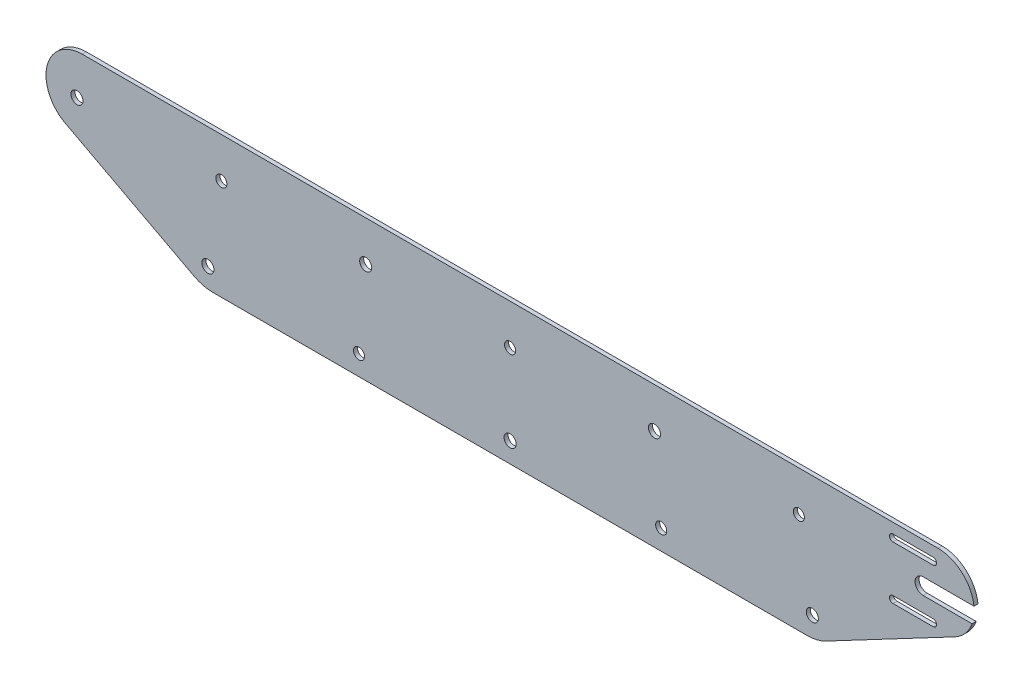
SolidWorks part; units mm, degrees
ref_plane "Plan de face" through (0, 0, 0) normal (0, 0, 1) x (1, 0, 0)
ref_plane "Plan de dessus" through (0, 0, 0) normal (0, 1, 0) x (1, 0, 0)
ref_plane "Plan de droite" through (0, 0, 0) normal (1, 0, 0) x (0, 0, -1)
sketch "Esquisse1" plane through (0, 0, 0) normal (0, 0, 1) x (1, 0, 0)
  line L0 (0, 0) -> (0, 122.747) construction
  line L1 (-215, -20) -> (215, -20) construction
  line L2 (-215, -20) -> (-215, 20) construction
  line L3 (-215, 20) -> (215, 20) construction
  line L4 (215, -20) -> (215, 20) construction
  line L5 (-215, -20) -> (215, 20) construction
  line L6 (-215, 20) -> (215, -20) construction
  line L7 (-1220, 0) -> (-150, 0) construction
  line L8 (-284.959, 40) -> (-150, 40)
  line L9 (150, 40) -> (284.959, 40)
  line L10 (150, 0) -> (150, -20) construction
  line L11 (150, -20) -> (-150, -20) construction
  line L12 (-150, 0) -> (-150, -20) construction
  line L13 (150, 0) -> (-150, -20) construction
  line L14 (150, -20) -> (-150, 0) construction
  line L15 (-284.959, 40) -> (-152.4795, -30)
  line L16 (-152.4795, -30) -> (152.4795, -30)
  line L17 (284.959, 40) -> (152.4795, -30)
  line L18 (-215, 20) -> (-71.6667, 20) construction
  line L19 (-71.6667, 20) -> (71.6667, 20) construction
  line L20 (71.6667, 20) -> (215, 20) construction
  line L21 (150, 0) -> (193.5165, 0) construction
  line L22 (150, 95) -> (-150, 95) construction
  line L23 (150, 95) -> (150, 40) construction
  line L24 (-150, 40) -> (150, 40)
  line L25 (-150, 95) -> (-150, 40) construction
  line L26 (150, 95) -> (-150, 0) construction
  line L27 (150, 0) -> (-150, 95) construction
  circle A0 centre (-215, 20) radius 3
  circle A1 centre (-150, -20) radius 3
  circle A2 centre (150, -20) radius 3
  circle A3 centre (215, 20) radius 3
  circle A4 centre (0, -20) radius 3
  circle A5 centre (-71.6667, 20) radius 3
  circle A6 centre (71.6667, 20) radius 3
  circle A7 centre (0, 78.03) radius 3 construction
  point P0 (0, 0)
  point P8 (0, -10)
  point P20 (0, 47.5)
  point P21 (0, -30)
  point P31 (0, 47.5)
  dimension "D8" = 6
  dimension "D10" = 58.03
  dimension "D1" = 430
  dimension "D2" = 40
  dimension "D3" = 300
  dimension "D4" = 20
  dimension "D5" = 15
  dimension "D6" = 10
  dimension "D7" = 10
  dimension "D9" = 55
extrude "Boss.-Extru.1" add sketch "Esquisse1" along normal blind 2
fillet "Congé1" radius 18 2 edges at (-284.959, 40, 1) (284.959, 40, 1)
fillet "Congé2" radius 20 2 edges at (-152.4795, -30, 1) (152.4795, -30, 1)
hole_wizard "Dégagement M31" positions "Esquisse3" profile "Esquisse2" hole size "M3" standard "Ansi Metric" end condition through all
sketch "Esquisse3" plane through (0, 0, 0) normal (0, 0, -1) x (-1, 0, 0)
  line L0 (-215, 12.5) -> (-215, 20)
  line L1 (-200, 6.7712) -> (-200, 33.2288)
  circle A0 centre (-215, 20) radius 7.5
  circle A1 centre (-215, 20) radius 20
  point P0 (-200, 33.2288)
  point P29 (-200, 6.7712)
  dimension "D2" = 15
  dimension "D3" = 40
  dimension "D1" = 15
sketch "Esquisse2" plane through (200, 33.2288, 0) normal (1, 0, 0) x (0, 1, 0)
  line L0 (0, 0) -> (0, 2)
  line L1 (0, 2) -> (1.7, 2)
  line L2 (1.7, 2) -> (1.7, 0)
  line L5 (1.7, 0) -> (0, 0)
  line L11 (0, -6.35) -> (0, 107.95) construction
  dimension "Diamètre du perçage jusqu'au prochain" = 3.4
  dimension "Profondeur du perçage jusqu'au prochain" = 2
sketch "Esquisse4" plane through (0, 0, 0) normal (0, 0, -1) x (-1, 0, 0)
  line L0 (-215, 24) -> (-230.2521, 24)
  line L1 (-215, 24) -> (-205, 24)
  line L2 (-215, 16) -> (-205, 16)
  line L3 (-215, 16) -> (-229.3341, 16)
  line L4 (-147.5205, -30) -> (147.5205, -30)
  line L5 (156.8641, -27.6833) -> (220.7728, 6.0851)
  line L6 (212.3636, 40) -> (-212.3636, 40)
  line L7 (-220.7728, 6.0851) -> (-156.8641, -27.6833)
  line L8 (-147.5205, -30) -> (147.5205, -30)
  line L9 (156.8641, -27.6833) -> (220.7728, 6.0851)
  line L10 (212.3636, 40) -> (-212.3636, 40)
  line L11 (-220.7728, 6.0851) -> (-156.8641, -27.6833)
  line L12 (-215, 16) -> (-215, 24)
  line L13 (-200, 34.9288) -> (-210, 34.9288)
  line L14 (-200, 34.9288) -> (-200, 31.5288)
  line L15 (-210, 31.5288) -> (-200, 31.5288)
  line L16 (-200, 31.5288) -> (-190, 31.5288)
  line L17 (-200, 8.4712) -> (-210, 8.4712)
  line L18 (-190, 34.9288) -> (-200, 34.9288)
  line L19 (-200, 8.4712) -> (-200, 5.0712)
  line L20 (-210, 5.0712) -> (-200, 5.0712)
  line L21 (-200, 5.0712) -> (-190, 5.0712)
  line L22 (-190, 8.4712) -> (-200, 8.4712)
  line L23 (-175, 14.2) -> (-185, 14.2)
  line L24 (-175, 14.2) -> (-175, 10.8)
  line L25 (-185, 10.8) -> (-175, 10.8)
  line L26 (-175, 10.8) -> (-165, 10.8)
  line L27 (-165, 14.2) -> (-175, 14.2)
  line L28 (-185, 14.2) -> (-228.5858, 14.2)
  line L29 (-185, 10.8) -> (-226.4547, 10.8)
  arc A2 (-205, 24) -> (-205, 16) centre (-205, 20) cw
  circle A3 centre (-215, 20) radius 3 construction
  arc A4 (147.5205, -30) -> (156.8641, -27.6833) centre (147.5205, -10) ccw
  arc A5 (220.7728, 6.0851) -> (212.3636, 40) centre (212.3636, 22) ccw
  arc A6 (-212.3636, 40) -> (-220.7728, 6.0851) centre (-212.3636, 22) ccw
  arc A7 (-156.8641, -27.6833) -> (-147.5205, -30) centre (-147.5205, -10) ccw
  arc A8 (147.5205, -30) -> (156.8641, -27.6833) centre (147.5205, -10) ccw
  arc A9 (220.7728, 6.0851) -> (212.3636, 40) centre (212.3636, 22) ccw
  arc A10 (-212.3636, 40) -> (-220.7728, 6.0851) centre (-212.3636, 22) ccw
  arc A11 (-156.8641, -27.6833) -> (-147.5205, -30) centre (-147.5205, -10) ccw
  circle A12 centre (-200, 33.2288) radius 1.7 construction
  circle A13 centre (-200, 33.2288) radius 1.7 construction
  arc A14 (-190, 34.9288) -> (-190, 31.5288) centre (-190, 33.2288) cw
  arc A15 (-210, 34.9288) -> (-210, 31.5288) centre (-210, 33.2288) ccw
  arc A16 (-190, 8.4712) -> (-190, 5.0712) centre (-190, 6.7712) cw
  arc A17 (-210, 8.4712) -> (-210, 5.0712) centre (-210, 6.7712) ccw
  arc A18 (-165, 14.2) -> (-165, 10.8) centre (-165, 12.5) cw
  circle A20 centre (-200, 6.7712) radius 1.7 construction
  point P17 (-215, 20)
  point P32 (-200, 33.2288)
  point P41 (-200, 6.7712)
  point P52 (-175, 12.5)
  dimension "D2" = 10
  dimension "D3" = 8
  dimension "D4" = 10
  dimension "D5" = 10
  dimension "D6" = 10
  dimension "D1" = 0
extrude "Enlèv. mat.-Extru.1" cut sketch "Esquisse4" against normal through all contours L3 A15 L0 A6 | A2 L1 A15 L2 | A14 L18 L2 L16 | L13 A15 L15 L2 | L17 A17 L20 L4 | A16 L22 L4 L21 region at (222.5529, 20.0401, 0) region at (208.3989, 20, 0) region at (205.6739, 33.2288, 0) region at (194.3261, 33.2288, 0) region at (205.6739, 6.7712, 0) region at (194.3261, 6.7712, 0)
hole_wizard "Dégagement M51" positions "Esquisse6" profile "Esquisse5" hole size "M5" standard "Ansi Metric" end condition through all
sketch "Esquisse6" plane through (0, 0, 0) normal (0, 0, -1) x (-1, 0, 0)
  line L0 (215, 20) -> (31.0935, 20) construction
  line L2 (215, 20) -> (143.3333, 20)
  line L4 (143.3333, 20) -> (71.6667, 20)
  line L5 (71.6667, 20) -> (0, 20)
  line L6 (0, 20) -> (-71.6667, 20)
  line L7 (-71.6667, 20) -> (-143.3333, 20)
  circle A2 centre (215, 20) radius 3
  circle A3 centre (215, 20) radius 3 construction
  circle A4 centre (-71.6667, 20) radius 3
  circle A5 centre (-71.6667, 20) radius 3 construction
  point P0 (143.3333, 20)
  point P2 (0, 20)
  point P37 (-143.3333, 20)
sketch "Esquisse5" plane through (-143.3333, 20, 0) normal (1, 0, 0) x (0, 1, 0)
  line L0 (0, 0) -> (0, 2)
  line L1 (0, 2) -> (2.75, 2)
  line L2 (2.75, 2) -> (2.75, 0)
  line L5 (2.75, 0) -> (0, 0)
  line L11 (0, -6.35) -> (0, 107.95) construction
  dimension "Diamètre du perçage jusqu'au prochain" = 5.5
  dimension "Profondeur du perçage jusqu'au prochain" = 2
hole_wizard "Dégagement M52" positions "Esquisse8" profile "Esquisse7" hole size "M5" standard "Ansi Metric" end condition through all
sketch "Esquisse8" plane through (0, 0, 2) normal (0, 0, 1) x (1, 0, 0)
  line L0 (-150, -20) -> (-75, -20)
  line L1 (-75, -20) -> (0, -20)
  line L2 (0, -20) -> (75, -20)
  line L3 (75, -20) -> (150, -20)
  point P0 (-75, -20)
  point P2 (75, -20)
sketch "Esquisse7" plane through (-75, -20, 2) normal (1, 0, 0) x (0, -1, 0)
  line L0 (0, 0) -> (0, 2)
  line L1 (0, 2) -> (2.75, 2)
  line L2 (2.75, 2) -> (2.75, 0)
  line L5 (2.75, 0) -> (0, 0)
  line L11 (0, -6.35) -> (0, 107.95) construction
  dimension "Diamètre du perçage jusqu'au prochain" = 5.5
  dimension "Profondeur du perçage jusqu'au prochain" = 2
